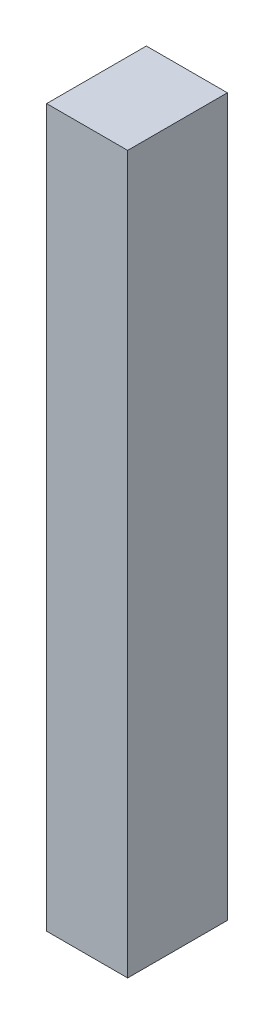
SolidWorks part; units mm, degrees
ref_plane "Спереди" through (0, 0, 0) normal (0, 0, 1) x (1, 0, 0)
ref_plane "Сверху" through (0, 0, 0) normal (0, 1, 0) x (1, 0, 0)
ref_plane "Справа" through (0, 0, 0) normal (1, 0, 0) x (0, 0, -1)
sketch "Эскиз1" plane through (0, 0, 0) normal (1, 0, 0) x (0, 0, -1)
  line L1 (16, -115) -> (-16, -115)
  line L2 (16, -115) -> (16, 115)
  line L3 (16, 115) -> (-16, 115)
  line L4 (-16, -115) -> (-16, 115)
  line L5 (16, -115) -> (-16, 115) construction
  line L6 (16, 115) -> (-16, -115) construction
  point P0 (0, 0)
  dimension "D1" = 230
  dimension "D2" = 32
extrude "Бобышка-Вытянуть1" add sketch "Эскиз1" along normal blind 26
